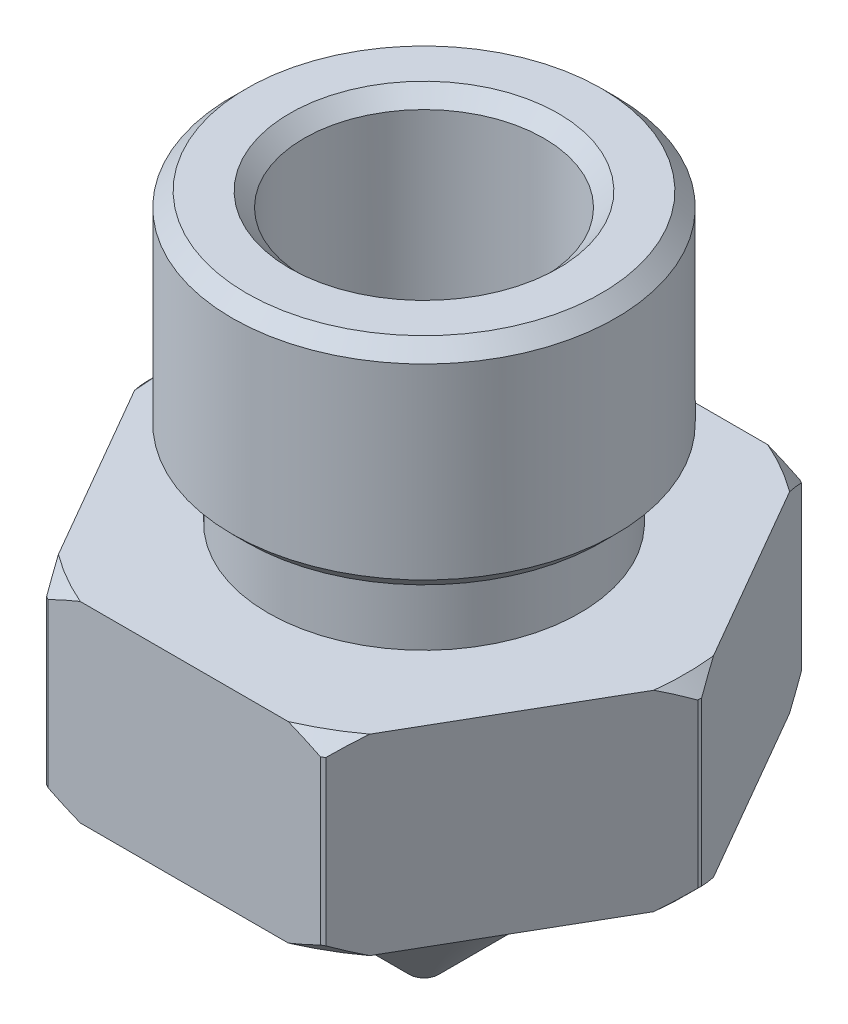
SolidWorks part; units mm, degrees
material "AISI 304"
ref_plane "Спереди" through (0, 0, 0) normal (0, 0, 1) x (1, 0, 0)
ref_plane "Сверху" through (0, 0, 0) normal (0, 1, 0) x (1, 0, 0)
ref_plane "Справа" through (0, 0, 0) normal (1, 0, 0) x (0, 0, -1)
ref_axis "ОсьX" through (-88.99, 0, 0) along (1, 0, 0)
ref_axis "ОсьZ" through (0, 55, 0) along (0, -1, 0)
ref_axis "ОсьY" through (0, 0, -88.99) along (0, 0, 1)
sketch "Эскиз1" plane through (0, 0, 0) normal (0, 0, 1) x (1, 0, 0)
  line L0 (0, 8.2669) -> (0, -10.3174) construction
  line L1 (2.5, 0) -> (4, 0)
  line L2 (4, 0) -> (4, -4.5)
  line L3 (4, -4.5) -> (3.25, -4.5)
  line L4 (3.25, -4.5) -> (3.25, -6)
  line L5 (3.25, -6) -> (5.75, -6)
  line L6 (5.75, -6) -> (5.75, -10)
  line L7 (5.75, -10) -> (4.3053, -10)
  line L8 (4.3053, -10) -> (0.3053, -14)
  line L9 (0.2, -13.2) -> (2.5, -10.459)
  line L10 (2.5, -10.459) -> (2.5, 0)
  line L11 (0.2, -13.2) -> (0.3053, -14)
  dimension "D1" = 5
  dimension "D2" = 0.4
  dimension "D3" = 7.5
  dimension "D4" = 0.8
  dimension "D5" = 8
  dimension "D6" = 6.5
  dimension "D7" = 6
  dimension "D8" = 1.5
  dimension "D9" = 11.5
  dimension "D10" = 4
  dimension "D11" = 45
  dimension "D12" = 40
  dimension "D13" = 4
revolve "Повернуть1" add sketch "Эскиз1" angle 360 mid plane about L0
cosmetic thread "Условное изображение резьбы1" parameters "D2"=6.917
chamfer "Фаска1" distance 0.3 angle 45 5 edges at (0, -10, 5.75) (0, -6, 5.75) (0, -4.5, 4) (0, 0, 2.5) (0, 0, 4)
sketch "Эскиз2" plane through (0, -6, 0) normal (0, 1, 0) x (1, 0, 0)
  line L1 (5.7735, 0) -> (2.8868, 5)
  line L2 (2.8868, 5) -> (-2.8868, 5)
  line L3 (-2.8868, 5) -> (-5.7735, 0)
  line L4 (-5.7735, 0) -> (-2.8868, -5)
  line L5 (-2.8868, -5) -> (2.8868, -5)
  line L6 (2.8868, -5) -> (5.7735, 0)
  circle A0 centre (0, 0) radius 5 construction
  dimension "D1" = 10
extrude "Вырез-Вытянуть1" cut sketch "Эскиз2" against normal through all flip side to cut
